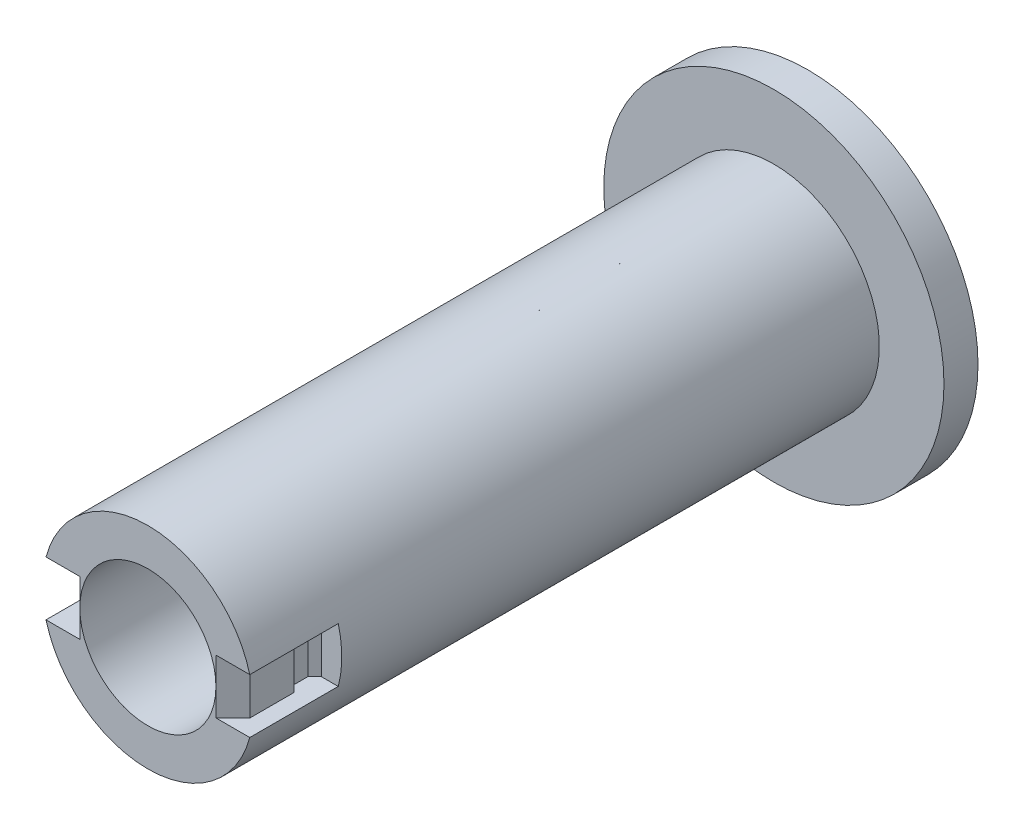
SolidWorks part; units mm, degrees
ref_plane "Front" through (0, 0, 0) normal (0, 0, 1) x (1, 0, 0)
ref_plane "Top" through (0, 0, 0) normal (0, 1, 0) x (1, 0, 0)
ref_plane "Right" through (0, 0, 0) normal (1, 0, 0) x (0, 0, -1)
sketch "Axle base sketch" plane through (0, 0, 0) normal (0, 0, 1) x (1, 0, 0)
  circle A0 centre (0, 0) radius 15.5
  dimension "D1" = 31
extrude "Axle" add sketch "Axle base sketch" along normal blind 92
sketch "Guard base" plane through (0, 0, 0) normal (0, 0, -1) x (-1, 0, 0)
  circle A0 centre (0, 0) radius 25
  dimension "D1" = 50
extrude "Guard" add sketch "Guard base" along normal blind 5
sketch "Inner axle hole base" plane through (0, 0, 92) normal (0, 0, 1) x (1, 0, 0)
  circle A0 centre (0, 0) radius 10
  dimension "D1" = 20
extrude "Inner axle hole" cut sketch "Inner axle hole base" against normal through all
sketch "Coupling tooth base" plane through (0, 0, 0) normal (0, 1, 0) x (1, 0, 0)
  line L0 (10, -92) -> (15.5, -92)
  line L1 (15.5, -92) -> (15.5, -79)
  line L2 (15.5, -92) -> (15.5, 0) construction
  line L3 (15.5, -79) -> (12.5, -79)
  line L5 (11.5, -82) -> (12.5, -83)
  line L6 (12.5, -83) -> (12.5, -89.5)
  line L7 (12.5, -89.5) -> (10, -92)
  line L9 (12.5, -79) -> (11.5, -80)
  line L10 (11.5, -80) -> (11.5, -82)
  dimension "D1" = 1
  dimension "D2" = 5.5
  dimension "D3" = 4
  dimension "D4" = 13
  dimension "D5" = 4
  dimension "D7" = 135
  dimension "D8" = 135
extrude "Coupling tooth hole" cut sketch "Coupling tooth base" against normal blind 4 and the other way blind 4 contours L9 L10 L5 L6 L7 L0 L1 L3 region at (13.7091, 0, 85.5933)
mirror "Coupling teeth" about plane through (0, 0, 0) normal (1, 0, 0) of "Coupling tooth hole"
equation "\"32_92_spool_inner_diameter\"=32"
equation "\"D1@Axle base sketch\"=\"32_92_spool_inner_diameter\"- \"spool_inner_diameter_room\""
equation "\"spool_inner_diameter_room\"=1"
equation "\"32_92_spool_thickness\"=92"
equation "\"D1@Axle\"=\"32_92_spool_thickness\""
equation "\"32_92_guard_diameter\"=50"
equation "\"D1@Guard base\"=\"32_92_guard_diameter\""
equation "\"guard_thickness\"=5"
equation "\"D1@Guard\"=\"guard_thickness\""
equation "\"large_inner_axle_diameter\"=20"
equation "\"D1@Inner axle hole base\"=\"large_inner_axle_diameter\""
equation "\"32_92_coupling_tooth_height\"=13"
equation "\"D4@Coupling tooth base\"=\"32_92_coupling_tooth_height\""
equation "\"32_92_coupling_tooth_thickness_total\"=4"
equation "\"D3@Coupling tooth base\"=\"32_92_coupling_tooth_thickness_total\""
equation "\"32_92_coupling_tooth_protrusion\"=1"
equation "\"D1@Coupling tooth base\"=\"32_92_coupling_tooth_protrusion\""
equation "\"32_92_coupling_tooth_depth\"=8"
equation "\"D1@Coupling tooth hole\"=\"32_92_coupling_tooth_depth\"/2"
equation "\"D2@Coupling tooth hole\"=\"32_92_coupling_tooth_depth\"/2"
equation "\"32_92_coupling_tooth_base_thickness\"=5.5"
equation "\"D2@Coupling tooth base\"=\"32_92_coupling_tooth_base_thickness\""
equation "\"32_92_coupling_tooth_head_height\"=4"
equation "\"D5@Coupling tooth base\"=\"32_92_coupling_tooth_head_height\""
